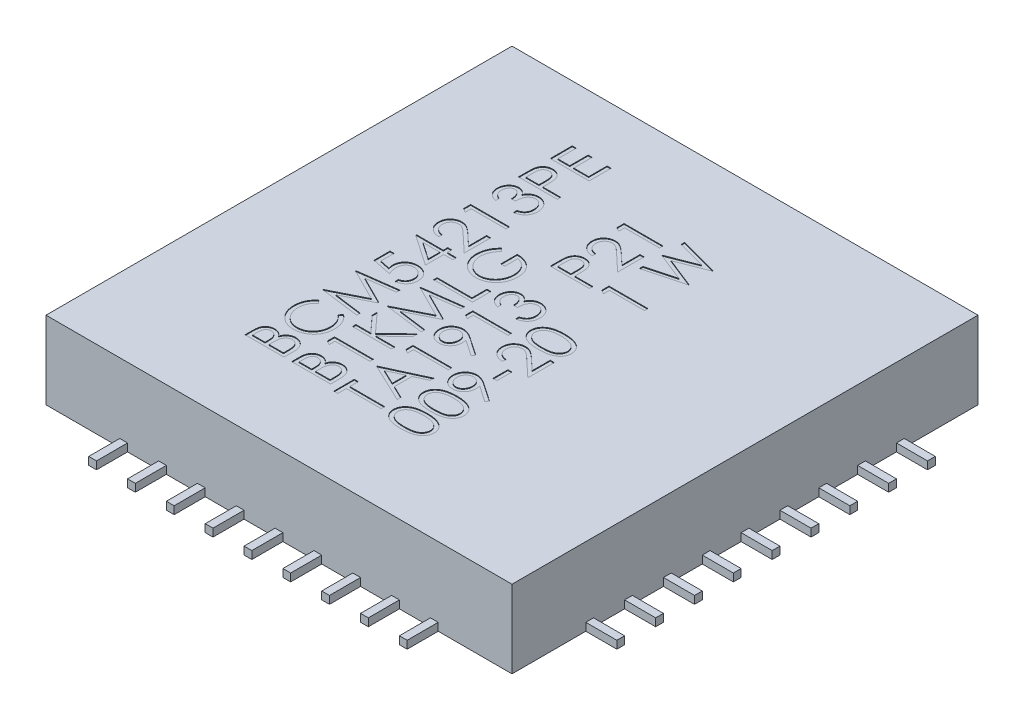
SolidWorks part; units mm, degrees
ref_plane "Front Plane" through (0, 0, 0) normal (0, 0, 1) x (1, 0, 0)
ref_plane "Top Plane" through (0, 0, 0) normal (0, 1, 0) x (1, 0, 0)
ref_plane "Right Plane" through (0, 0, 0) normal (1, 0, 0) x (0, 0, -1)
sketch "BaseS" plane through (0, 0, 0) normal (0, 1, 0) x (1, 0, 0)
  line L1 (-3, 3) -> (3, 3)
  line L2 (-3, 3) -> (-3, -3)
  line L3 (-3, -3) -> (3, -3)
  line L4 (3, 3) -> (3, -3)
  line L5 (-3, 3) -> (3, -3) construction
  line L6 (-3, -3) -> (3, 3) construction
  point P0 (0, 0)
  dimension "W" = 6
  dimension "L" = 6
extrude "Base" add sketch "BaseS" along normal blind 1
sketch "SolderConnectionS" plane through (0, 0, 0) normal (0, 1, 0) x (1, 0, 0)
  line L0 (3, -2) -> (3.4, -2)
  line L1 (3, -3) -> (3, 3) construction
  dimension "XDim" = 1
  dimension "Length" = 0.4
extrude "SolderConnection" add sketch "SolderConnectionS" along normal blind 0.1 thin thin type mid plane wall 0.1
pattern_linear "SC LP" count 9 spacing 0.5 along (0, 0, -1) of "SolderConnection"
ref_axis "AxisSC" through (0, 1.05, 0) along (0, -1, 0)
pattern_circular "SC CP" count 4 over 360 about axis through (0, 1.05, 0) along (0, -1, 0) of "SolderConnection", "SC LP"
sketch "PartNoS" plane through (0, 1, 0) normal (0, 1, 0) x (1, 0, 0)
  line L0 (-1, -2) -> (-1, 3) construction
  line L1 (3, 3) -> (-3, 3) construction
  line L2 (-3, -3) -> (3, -3) construction
  line L3 (-3, 3) -> (-3, -3) construction
  line L5 (-0.4, -2) -> (-0.4, 3) construction
  line L6 (0.2, -2) -> (0.2, 3) construction
  line L7 (0.8, -2) -> (0.8, 3) construction
  line L8 (-1, -2) -> (-0.4, -2) construction
  line L9 (-0.4, -2) -> (0.2, -2) construction
  line L10 (0.2, -2) -> (0.8, -2) construction
  text T0 "BCM54213PE" font "Century Gothic" height 0.5
  dimension "YDim" = 2
  dimension "XDim" = 1
  dimension "YDist" = 0.6
extrude "PartNo" cut sketch "PartNoS" against normal blind 0.01
sketch "PartNoSE1" plane through (0, 1, 0) normal (0, 1, 0) x (1, 0, 0)
  text T0 "B1KMLG" font "Century Gothic" height 0.5
sketch "PartNoSE2" plane through (0, 1, 0) normal (0, 1, 0) x (1, 0, 0)
  text T0 "TA1913  P21" font "Century Gothic" height 0.5
sketch "PartNoSE3" plane through (0, 1, 0) normal (0, 1, 0) x (1, 0, 0)
  text T0 "009-20   1 W" font "Century Gothic" height 0.5
extrude "PartNoE1" cut sketch "PartNoSE1" against normal up to surface (0.01 mm away) up to face at (-1.1429, 0.99, 1.8178)
extrude "PartNoE2" cut sketch "PartNoSE2" against normal up to surface (0.01 mm away) up to face at (-1.1429, 0.99, 1.8178)
extrude "PartNoE3" cut sketch "PartNoSE3" against normal up to surface (0.01 mm away) up to face at (-1.1429, 0.99, 1.8178)
